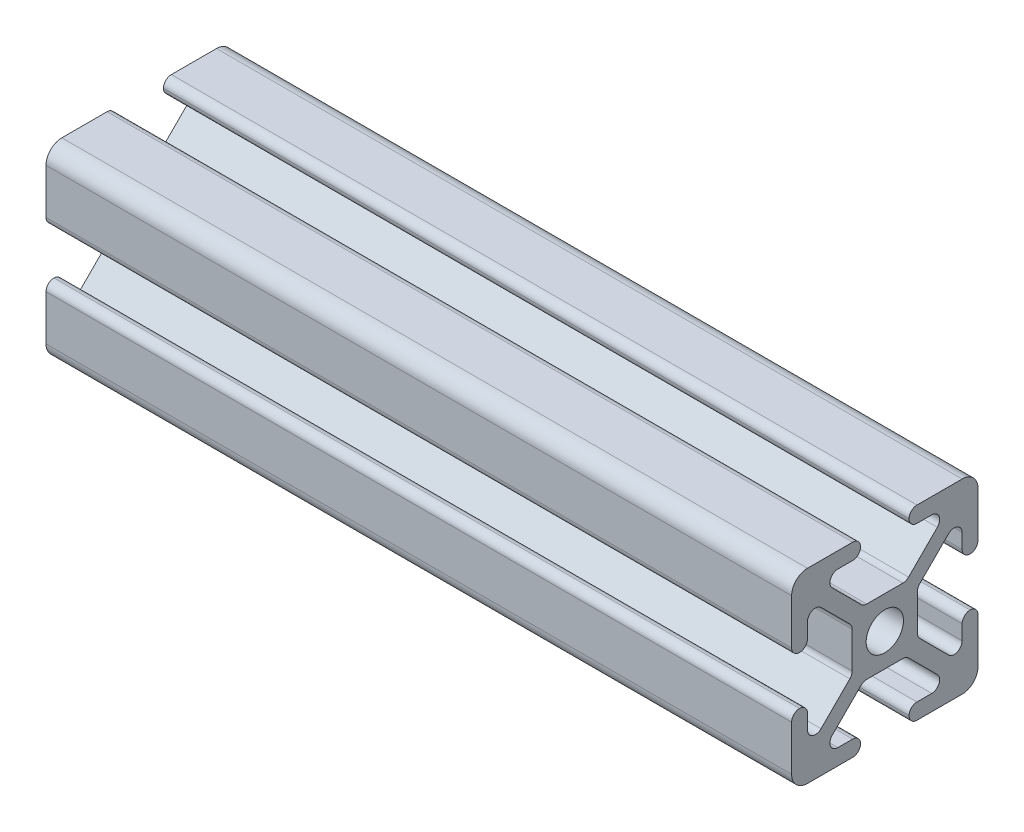
SolidWorks part; units mm, degrees
ref_plane "Front Plane" through (0, 0, 0) normal (1, 0, 0) x (0, 1, 0)
ref_plane "Top Plane" through (0, 0, 0) normal (0, 0, 1) x (0, 1, 0)
ref_plane "Right Plane" through (0, 0, 0) normal (0, 1, 0) x (-1, 0, 0)
sketch "Sketch1" plane through (0, 0, 0) normal (1, 0, 0) x (0, 1, 0)
  line L0 (0, 0) -> (0, 12.5) construction
  line L1 (-12.5, -12.5) -> (12.5, -12.5)
  line L2 (-12.5, -12.5) -> (-12.5, 12.5)
  line L3 (-12.5, 12.5) -> (12.5, 12.5)
  line L4 (12.5, -12.5) -> (12.5, 12.5)
  line L5 (-12.5, -12.5) -> (12.5, 12.5) construction
  line L6 (-12.5, 12.5) -> (12.5, -12.5) construction
  line L7 (-3.25, 12.5) -> (-3.25, 10.37)
  line L8 (-3.25, 10.37) -> (-8.8639, 10.37)
  line L9 (-8.8639, 10.37) -> (-2.8739, 4.38)
  line L10 (-2.8739, 4.38) -> (2.8739, 4.38)
  line L11 (8.8639, 10.37) -> (2.8739, 4.38)
  line L12 (3.25, 10.37) -> (8.8639, 10.37)
  line L13 (3.25, 12.5) -> (3.25, 10.37)
  line L14 (12.5, -3.25) -> (10.37, -3.25)
  line L15 (10.37, -3.25) -> (10.37, -8.8639)
  line L16 (10.37, -8.8639) -> (4.38, -2.8739)
  line L17 (4.38, 2.8739) -> (4.38, -2.8739)
  line L18 (10.37, 8.8639) -> (4.38, 2.8739)
  line L19 (10.37, 3.25) -> (10.37, 8.8639)
  line L20 (12.5, 3.25) -> (10.37, 3.25)
  line L21 (-3.25, -12.5) -> (-3.25, -10.37)
  line L22 (-3.25, -10.37) -> (-8.8639, -10.37)
  line L23 (-8.8639, -10.37) -> (-2.8739, -4.38)
  line L24 (2.8739, -4.38) -> (-2.8739, -4.38)
  line L25 (8.8639, -10.37) -> (2.8739, -4.38)
  line L26 (3.25, -10.37) -> (8.8639, -10.37)
  line L27 (3.25, -12.5) -> (3.25, -10.37)
  line L28 (-12.5, 3.25) -> (-10.37, 3.25)
  line L29 (-10.37, 3.25) -> (-10.37, 8.8639)
  line L30 (-10.37, 8.8639) -> (-4.38, 2.8739)
  line L31 (-4.38, -2.8739) -> (-4.38, 2.8739)
  line L32 (-10.37, -8.8639) -> (-4.38, -2.8739)
  line L33 (-10.37, -3.25) -> (-10.37, -8.8639)
  line L34 (-12.5, -3.25) -> (-10.37, -3.25)
  circle A0 centre (0, 0) radius 2.5
  point P0 (0, 0)
  point P15 (0, 4.38)
  dimension "D3" = 5
  dimension "D1" = 25
  dimension "D2" = 25
  dimension "D4" = 2.13
  dimension "D5" = 2.13
  dimension "D6" = 6.5
  dimension "D7" = 4.38
  dimension "D8" = 4
extrude "Boss-Extrude1" add sketch "Sketch1" along normal blind 100 contours L34 L2 L1 L21 L22 L23 L24 L25 L26 L27 L4 L14 L15 L16 L17 L18 L19 L20 L3 L13 L12 L11 L10 L9 L8 L7 L28 L29 L30 L31 L32 L33 A0 region at (0, -12.1464, -7.875)
fillet "Fillet1" radius 1.065 32 edges at (50, -10.37, -8.8639) (50, 2.8739, -4.38) (50, -2.8739, -4.38) (50, -4.38, 2.8739) (50, -4.38, -2.8739) (50, -2.8739, 4.38) (50, 2.8739, 4.38) (50, 4.38, 2.8739) (50, 4.38, -2.8739) (50, -8.8639, -10.37) (50, 8.8639, -10.37) (50, 10.37, -8.8639) (50, -10.37, 8.8639) (50, -8.8639, 10.37) (50, 10.37, 8.8639) (50, 8.8639, 10.37) (50, 12.5, 3.25) (50, -3.25, -12.5) (50, -10.37, 3.25) (50, 10.37, 3.25) (50, -10.37, -3.25) (50, -12.5, -3.25) (50, -12.5, 3.25) (50, 3.25, -10.37) (50, -3.25, -10.37) (50, 3.25, -12.5) (50, 10.37, -3.25) (50, 12.5, -3.25) (50, 3.25, 12.5) (50, 3.25, 10.37) (50, -3.25, 10.37) (50, -3.25, 12.5)
fillet "Fillet2" radius 2.13 4 edges at (50, 12.5, -12.5) (50, -12.5, -12.5) (50, 12.5, 12.5) (50, -12.5, 12.5)
